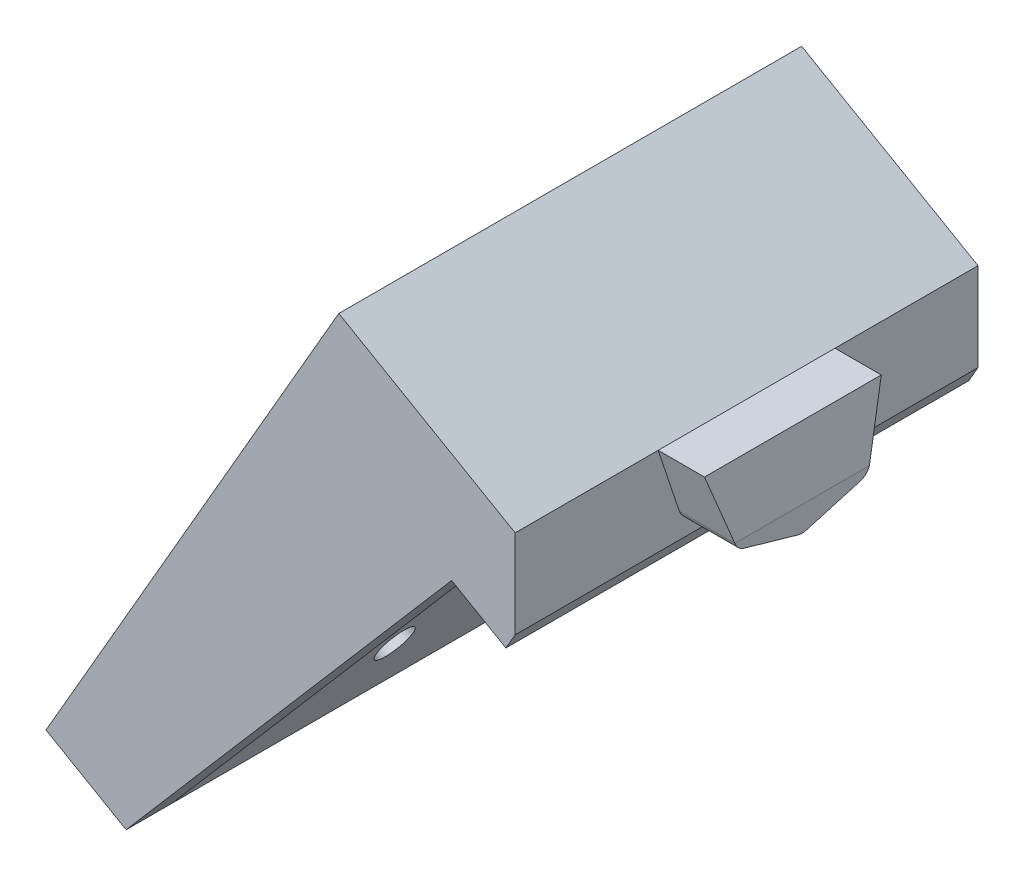
SolidWorks part; units mm, degrees
ref_plane "Piano frontale" through (0, 0, 0) normal (0, 0, 1) x (1, 0, 0)
ref_plane "Piano superiore" through (0, 0, 0) normal (0, 1, 0) x (1, 0, 0)
ref_plane "Piano destro" through (0, 0, 0) normal (1, 0, 0) x (0, 0, -1)
sketch "Sketch1" plane through (0, 0, 0) normal (1, 0, 0) x (0, 0, -1)
  line L0 (-9.55, 0) -> (9.55, 0)
  line L1 (9.55, 0) -> (7.0174, -7.5885)
  line L2 (7.0174, -7.5885) -> (0, -9.6)
  line L3 (0, -9.6) -> (0, 0) construction
  line L4 (-7.0174, -7.5885) -> (0, -9.6)
  line L5 (-9.55, 0) -> (-7.0174, -7.5885)
  dimension "D1" = 7.3
  dimension "D2" = 8
  dimension "D3" = 9.55
  dimension "D4" = 9.6
extrude "Boss-Extrude1" add sketch "Sketch1" along normal blind 6
fillet "Fillet1" radius 1.5 3 edges at (3, -7.5885, 7.0174) (3, -9.6, 0) (3, -7.5885, -7.0174)
sketch "Sketch2" plane through (0, 0, 0) normal (0, 0, 1) x (1, 0, 0)
  line L0 (0, 0) -> (-19.0526, 11)
  line L1 (0, 0) -> (0, -9.5396)
  line L2 (-19.0526, 11) -> (-50.6833, -43.7861)
  line L3 (-50.6833, -43.7861) -> (-42.0231, -48.7861)
  line L4 (-42.0231, -48.7861) -> (-14.5231, -1.1547)
  line L5 (-14.5231, -1.1547) -> (0, -9.5396)
  line L6 (0, 0) -> (0, -6.8392) construction
  dimension "D1" = 60
  dimension "D2" = 10
  dimension "D3" = 22
  dimension "D4" = 55
extrude "Boss-Extrude2" add sketch "Sketch2" against normal blind 25 and the other way blind 25 contours L2 L3 L4 L5 L1 L0
sketch "Sketch10" plane through (0, 0, 25) normal (0, 0, 1) x (1, 0, 0)
  line L0 (6, 0) -> (6, -6.8392)
  line L1 (6, -6.8392) -> (5, 0)
  line L2 (6, 0) -> (0, 0) construction
  line L3 (5, 0) -> (6, 0)
  dimension "D1" = 1
extrude "Cut-Extrude1" cut sketch "Sketch10" against normal through all
sketch "Sketch14" plane through (-4.1308, -7.1547, 0) normal (-0.5, -0.866, 0) x (0.866, -0.5, 0)
  line L5 (-12, 25) -> (-12, -25)
  line L6 (-12, -25) -> (4.7698, -25)
  line L7 (4.7698, -25) -> (4.7698, 0)
  line L8 (4.7698, 0) -> (4.7698, 25)
  line L9 (4.7698, 25) -> (-12, 25)
  line L10 (-12, 25) -> (-12, -25)
  line L11 (-12, -25) -> (4.7698, -25)
  line L12 (4.7698, -25) -> (4.7698, 0)
  line L13 (4.7698, 0) -> (4.7698, 25)
  line L14 (4.7698, 25) -> (-12, 25)
  dimension "D1" = 0
extrude "Boss-Extrude3" add sketch "Sketch14" along normal blind 2
sketch "Sketch11" plane through (-19.0526, 11, 0) normal (-0.866, 0.5, 0) x (0, 0, 1)
  line L1 (0, -3.3) -> (0, 3.3) construction
  point P0 (0, -40.2615)
  point P1 (0, -55.2615)
  dimension "D1" = 30
  dimension "D2" = 15
hole_wizard "Ø4.0 (4) Diameter Hole1" positions "Sketch11" profile "Sketch12" hole size "Ø4.0" standard "ISO" end condition up to next
sketch "Sketch12" plane through (-39.1833, -23.8675, 0) normal (0, 0, 1) x (-0.5, -0.866, 0)
  line L0 (0, 0) -> (0, 10)
  line L1 (0, 10) -> (2, 10)
  line L2 (2, 10) -> (2, 0)
  line L5 (2, 0) -> (0, 0)
  line L11 (0, -6.35) -> (0, 107.95) construction
  dimension "Thru Hole Dia." = 4
  dimension "Thru Hole Depth" = 10
sketch "Sketch15" plane through (-19.0526, 11, 0) normal (-0.866, 0.5, 0) x (-0.5, -0.866, 0)
  circle A0 centre (40.2615, 0) radius 3.75
  circle A1 centre (55.2615, 0) radius 3.75
  dimension "D1" = 7.5
  dimension "D2" = 7.5
extrude "Cut-Extrude2" cut sketch "Sketch15" against normal blind 3
sketch "Sketch16" plane through (-10.3923, 6, 0) normal (0.866, -0.5, 0) x (0, 0, -1)
  line L0 (-25, -63.2615) -> (25, -63.2615) construction
  line L1 (-25, -10.2615) -> (-20, -10.2615)
  line L2 (-25, -10.2615) -> (-25, -63.2615)
  line L3 (-25, -63.2615) -> (-20, -63.2615)
  line L4 (-20, -10.2615) -> (-20, -63.2615)
  dimension "D1" = 5
extrude "Boss-Extrude4" add sketch "Sketch16" along normal blind 10
mirror "Mirror1" about plane through (0, 0, 0) normal (0, 0, 1) of "Boss-Extrude4"
sketch "Sketch17" plane through (0, 0, -20) normal (0, 0, 1) x (1, 0, 0)
  line L0 (-42.0231, -48.7861) -> (-6.8628, -7.8867)
  line L1 (-6.8628, -7.8867) -> (-33.3628, -53.7861)
  line L2 (-33.3628, -53.7861) -> (-42.0231, -48.7861)
extrude "Cut-Extrude3" cut sketch "Sketch17" against normal blind 10 and the other way through all
